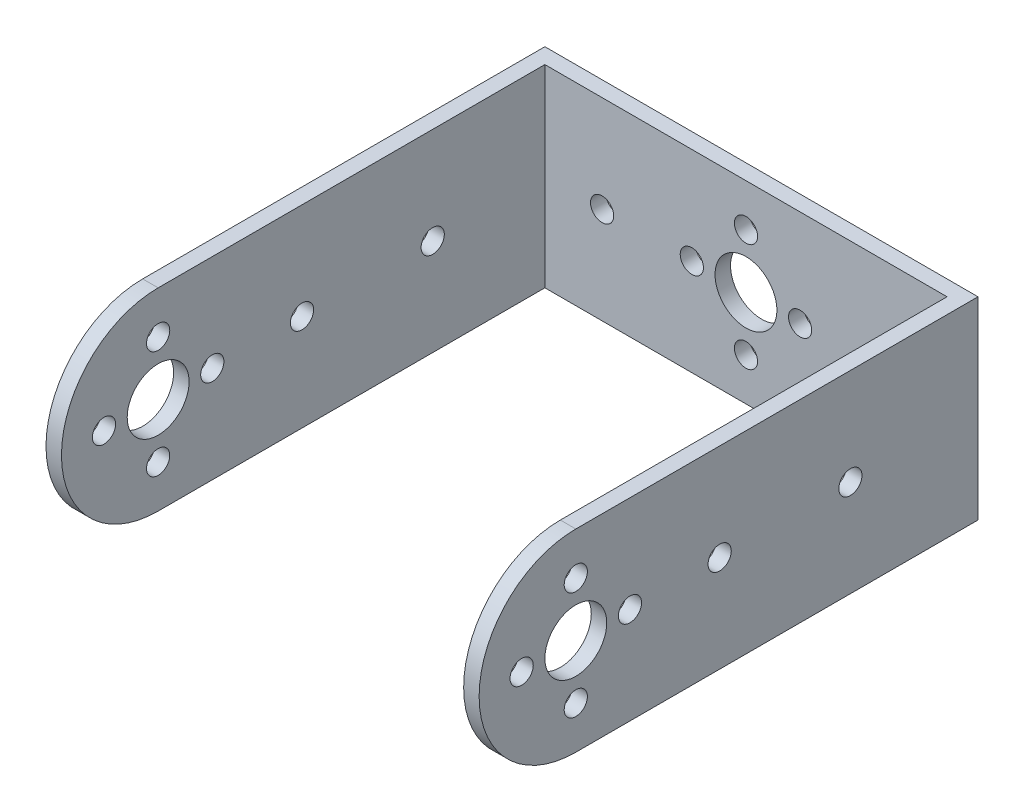
SolidWorks part; units mm, degrees
ref_plane "前视基准面" through (0, 0, 0) normal (0, 0, 1) x (1, 0, 0)
ref_plane "上视基准面" through (0, 0, 0) normal (0, 1, 0) x (1, 0, 0)
ref_plane "右视基准面" through (0, 0, 0) normal (1, 0, 0) x (0, 0, -1)
sketch "草图1" plane through (0, 0, 0) normal (0, 0, 1) x (1, 0, 0)
  line L1 (-28, 12.5) -> (28, 12.5)
  line L2 (-28, 12.5) -> (-28, -12.5)
  line L3 (-28, -12.5) -> (28, -12.5)
  line L4 (28, 12.5) -> (28, -12.5)
  line L5 (-28, 12.5) -> (28, -12.5) construction
  line L6 (-28, -12.5) -> (28, 12.5) construction
  point P0 (0, 0)
  dimension "D1" = 56
  dimension "D2" = 25
extrude "凸台-拉伸1" add sketch "草图1" along normal blind 64.5
sketch "草图2" plane through (0, -12.5, 0) normal (0, -1, 0) x (1, 0, 0)
  line L0 (0, 45.8587) -> (0, -3.5149) construction
  line L1 (-28, 64.5) -> (28, 64.5) construction
  line L2 (0, 64.5) -> (26, 64.5)
  line L3 (26, 64.5) -> (26, 2)
  line L4 (26, 2) -> (-26, 2)
  line L5 (-26, 2) -> (-26, 64.5)
  line L6 (0, 64.5) -> (-26, 64.5)
  point P3 (0, 64.5)
  point P13 (-28, 64.5)
extrude "切除-拉伸1" cut sketch "草图2" against normal through all
sketch "草图3" plane through (28, 0, 0) normal (1, 0, 0) x (0, 0, -1)
  line L0 (-52, 12.5) -> (-64.5, 12.5)
  line L1 (-64.5, 12.5) -> (-64.5, -12.5)
  line L4 (-64.5, -12.5) -> (-52, -12.5)
  line L5 (0, 0) -> (-52, 0) construction
  arc A0 (-52, 12.5) -> (-52, -12.5) centre (-52, 0) ccw
  line M4 (0, 12.5) -> (-64.5, 12.5)
  line M5 (-64.5, 12.5) -> (-64.5, -12.5)
  line M6 (-64.5, -12.5) -> (0, -12.5)
sketch "草图4" plane through (0, 0, 2) normal (0, 0, 1) x (1, 0, 0)
  line L0 (-32.0699, 0) -> (34.4869, 0) construction
  line L1 (0, 16.1115) -> (0, -17.9038) construction
  circle A0 centre (0, 0) radius 4
  circle A1 centre (0, 0) radius 7 construction
  circle A2 centre (0, 7) radius 1.5
  circle A3 centre (0, -7) radius 1.5
  circle A4 centre (-7, 0) radius 1.5
  circle A5 centre (7, 0) radius 1.5
  circle A6 centre (18.6, 0) radius 1.5
  circle A7 centre (-18.6, 0) radius 1.5
  dimension "D1" = 18.6
extrude "切除-拉伸3" cut sketch "草图4" against normal through all
extrude "切除-拉伸4" cut sketch "草图3" against normal through all contours A0 M4 M5 | A0 L1 M6 region at (28, 9.7079, 61.7079) region at (28, -9.7079, 61.7079)
sketch "草图5" plane through (28, 0, 0) normal (1, 0, 0) x (0, 0, -1)
  line L0 (-52, 0) -> (-33.4, 0) construction
  line L1 (-33.4, 0) -> (-16.5, 0) construction
  circle A0 centre (-52, 0) radius 4
  circle A1 centre (-52, 0) radius 7 construction
  circle A2 centre (-52, 7) radius 1.5
  circle A3 centre (-59, 0) radius 1.5
  circle A4 centre (-52, -7) radius 1.5
  circle A5 centre (-45, 0) radius 1.5
  circle A6 centre (-33.4, 0) radius 1.5
  circle A7 centre (-16.5, 0) radius 1.5
  point P2 (-52, 0)
extrude "切除-拉伸5" cut sketch "草图5" against normal through all
